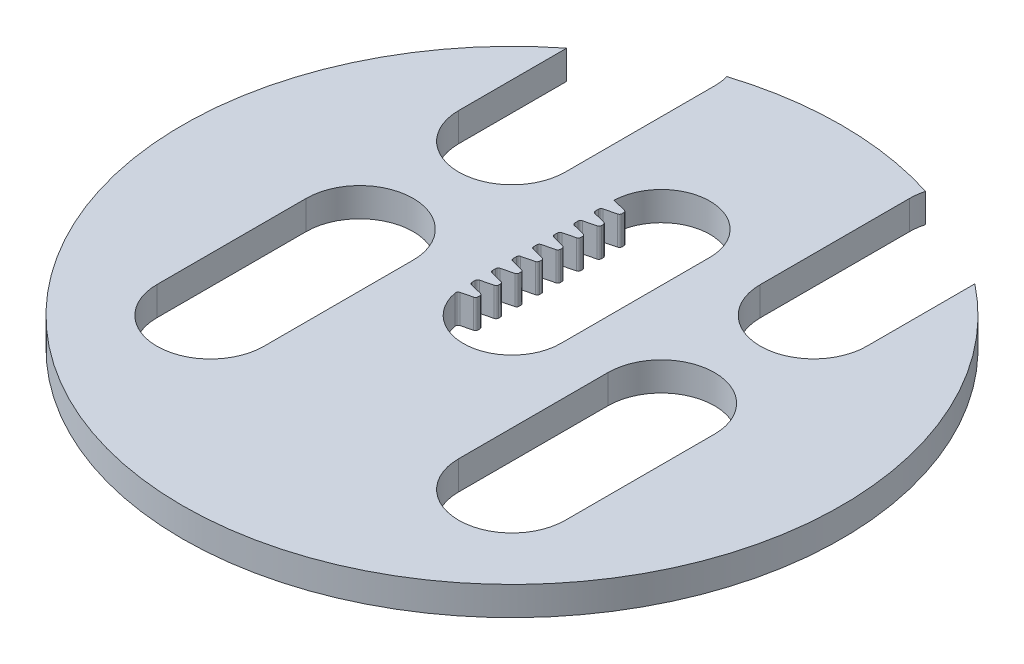
SolidWorks part; units mm, degrees
ref_plane "Front Plane" through (0, 0, 0) normal (0, 0, 1) x (1, 0, 0)
ref_plane "Top Plane" through (0, 0, 0) normal (0, 1, 0) x (1, 0, 0)
ref_plane "Right Plane" through (0, 0, 0) normal (1, 0, 0) x (0, 0, -1)
sketch "Sketch3" plane through (0, 0, 0) normal (0, -1, 0) x (1, 0, 0)
  line L0 (0, 0) -> (0, -17.78) construction
  line L1 (5.8, 0) -> (5.8, -17.78)
  line L2 (-5.8, 0) -> (-5.8, -17.78)
  line L3 (-17.9605, -35.7405) -> (17.9605, 0.1805) construction
  line L4 (-17.9605, 0.1805) -> (17.9605, -35.7405) construction
  line L5 (-17.9605, 0.1805) -> (17.9605, 0.1805) construction
  line L6 (-17.9605, 0.1805) -> (-17.9605, 17.9605) construction
  line L7 (-24.3305, 0.1805) -> (-24.3305, 17.9605)
  line L8 (-11.5905, 0.1805) -> (-11.5905, 17.9605)
  line L9 (-17.9605, -35.7405) -> (-17.9605, -17.9605) construction
  line L10 (-24.3105, -35.7405) -> (-24.3105, -17.9605)
  line L11 (-11.6105, -35.7405) -> (-11.6105, -17.9605)
  line L12 (17.9605, 0.1805) -> (17.9605, 17.9605) construction
  line L13 (11.6105, 0.1805) -> (11.6105, 17.9605)
  line L14 (24.3105, 0.1805) -> (24.3105, 17.9605)
  line L15 (17.9605, -35.7405) -> (17.9605, -17.9605) construction
  line L16 (11.6105, -35.7405) -> (11.6105, -17.9605)
  line L17 (24.3105, -35.7405) -> (24.3105, -17.9605)
  circle A0 centre (0, 0) radius 39.2557
  arc A1 (5.8, 0) -> (-5.8, 0) centre (0, 0) ccw
  arc A2 (-5.8, -17.78) -> (5.8, -17.78) centre (0, -17.78) ccw
  arc A3 (-24.3305, 0.1805) -> (-11.5905, 0.1805) centre (-17.9605, 0.1805) ccw
  arc A4 (-11.5905, 17.9605) -> (-24.3305, 17.9605) centre (-17.9605, 17.9605) ccw
  arc A5 (-24.3105, -35.7405) -> (-11.6105, -35.7405) centre (-17.9605, -35.7405) ccw
  arc A6 (-11.6105, -17.9605) -> (-24.3105, -17.9605) centre (-17.9605, -17.9605) ccw
  arc A7 (11.6105, 0.1805) -> (24.3105, 0.1805) centre (17.9605, 0.1805) ccw
  arc A8 (24.3105, 17.9605) -> (11.6105, 17.9605) centre (17.9605, 17.9605) ccw
  arc A9 (11.6105, -35.7405) -> (24.3105, -35.7405) centre (17.9605, -35.7405) ccw
  arc A10 (24.3105, -17.9605) -> (11.6105, -17.9605) centre (17.9605, -17.9605) ccw
  point P5 (0, -8.89)
  point P10 (-17.9605, 9.0705)
  point P13 (0, -17.78)
  point P16 (0, -17.78)
  point P22 (-17.9605, -26.8505)
  point P28 (17.9605, 9.0705)
  point P34 (17.9605, -26.8505)
  dimension "D1" = 78.5114
  dimension "D3" = 5.8
  dimension "D8" = 6.37
  dimension "D10" = 6.35
  dimension "D13" = 6.35
  dimension "D14" = 6.35
  dimension "D2" = 17.78
  dimension "D4" = 45
  dimension "D5" = 45
  dimension "D6" = 50.8
extrude "Boss-Extrude1" add sketch "Sketch3" along normal blind 3.175 and the other way blind 0.254 contours L17 A10 L16 A0 L11 A6 L10 L2 A2 L1 A1 L8 A4 L7 A3 L14 A8 L13 A7 region at (-16.6428, 0, 34.3233)
sketch "Sketch4" plane through (0, 0.254, 0) normal (0, 1, 0) x (1, 0, 0)
  line L0 (-5.8, 0) -> (-3.94, 0) construction
  line L1 (-3.94, -0.34) -> (-3.94, 0.34)
  line L2 (-3.94, 0.34) -> (-5.8, 0.8038)
  line L3 (-5.8, 0) -> (-5.8, 17.78) construction
  line L8 (-5.8, 0.8038) -> (-5.8, -0.8038)
  line L9 (-5.8, -0.8038) -> (-3.94, -0.34)
  point P7 (-3.94, 0)
  line M5 (-5.8, 0) -> (-5.8, 17.78)
  arc M8 (5.8, 0) -> (-5.8, 0) centre (0, 0) cw
  dimension "D3" = 76
  dimension "D1" = 1.86
  dimension "D2" = 0.34
extrude "Boss-Extrude2" add sketch "Sketch4" against normal up to surface (3.429 mm away) contours L1 L2 M5 M8 | L0 L9 L1 M8 | L8 L9 M8 region at (-4.9957, 0.254, -0.3016) region at (-5.7837, 0.254, 0.5979) region at (-4.9847, 0.254, 0.2975) up to face at (0, -3.175, -8.89)
pattern_linear "LPattern1" count 8 spacing 2.45 along (0, 0, -1) of "Boss-Extrude2"
fillet "Fillet1" radius 0.3 31 edges at (-3.94, -1.4605, 0.34) (-5.8, -1.4605, -1.6462) (-3.94, -1.4605, -2.11) (-3.94, -1.4605, -2.79) (-5.8, -1.4605, -3.2538) (-5.8, -1.4605, -4.0962) (-3.94, -1.4605, -4.56) (-3.94, -1.4605, -5.24) (-5.8, -1.4605, -5.7038) (-5.8, -1.4605, -6.5462) (-3.94, -1.4605, -7.01) (-3.94, -1.4605, -7.69) (-5.8, -1.4605, -8.1538) (-5.8, -1.4605, -8.9962) (-3.94, -1.4605, -9.46) (-3.94, -1.4605, -10.14) (-5.8, -1.4605, -10.6038) (-5.8, -1.4605, -11.4462) (-3.94, -1.4605, -11.91) (-3.94, -1.4605, -12.59) (-5.8, -1.4605, -13.0538) (-5.8, -1.4605, -13.8962) (-3.94, -1.4605, -14.36) (-3.94, -1.4605, -15.04) (-5.8, -1.4605, -15.5038) (-5.8, -1.4605, -16.3462) (-3.94, -1.4605, -16.81) (-3.94, -1.4605, -17.49) (-5.7459, -1.4605, 0.7903) (-5.8, -1.4605, -0.8038) (-3.94, -1.4605, -0.34)
equation "\"AIRFRAME_OD\"= 3.091in"
equation "\"AIRFRAME_ID\"= 3.00in"
equation "\"FLAT_T\"= 0.125in"
equation "\"COUPLER_OD\"= 2.998in"
equation "\"COUPLER_ID\"= 2.875in"
equation "\"NOSE_EXP_L\"= 3.5in"
equation "\"NOSE_SHOULDER_L\"= 5in"
equation "\"MAIN_L\"= 30in"
equation "\"RECO_COUP_L\"= 6in"
equation "\"RECO_SWITCH_L\"= 1.5in"
equation "\"RECO_ROD_X\"= 1.5in"
equation "\"DROGUE_L\"= 14in"
equation "\"ATS_FORE_COUP_L\"= 4in"
equation "\"ATS_AFT_COUP_L\"= 2.5in"
equation "\"ATS_ROD_X\"= 2in"
equation "\"LOWER_L\"= 16in"
equation "\"FIN_ROOT\"= 5in"
equation "\"FIN_X\"= 0.75in"
equation "\"FIN_N\"= 4"
equation "\"MOTOR_OD\"= 2.25in"
equation "\"MOTOR_ID\"= 2.126in"
equation "\"MOTOR_L\"= 8in"
equation "\"MOTOR_LOWER_X\"= 0.5in"
equation "\"CR_AFT_X\"= 0.5in"
equation "\"CR_FORE_X\"= 6in"
equation "\"D1@Boss-Extrude1\"=\"FLAT_T\""
equation "\"D1@Sketch3\"=\"AIRFRAME_OD\""
equation "\"D6@Sketch3\"=\"ATS_ROD_X\""
